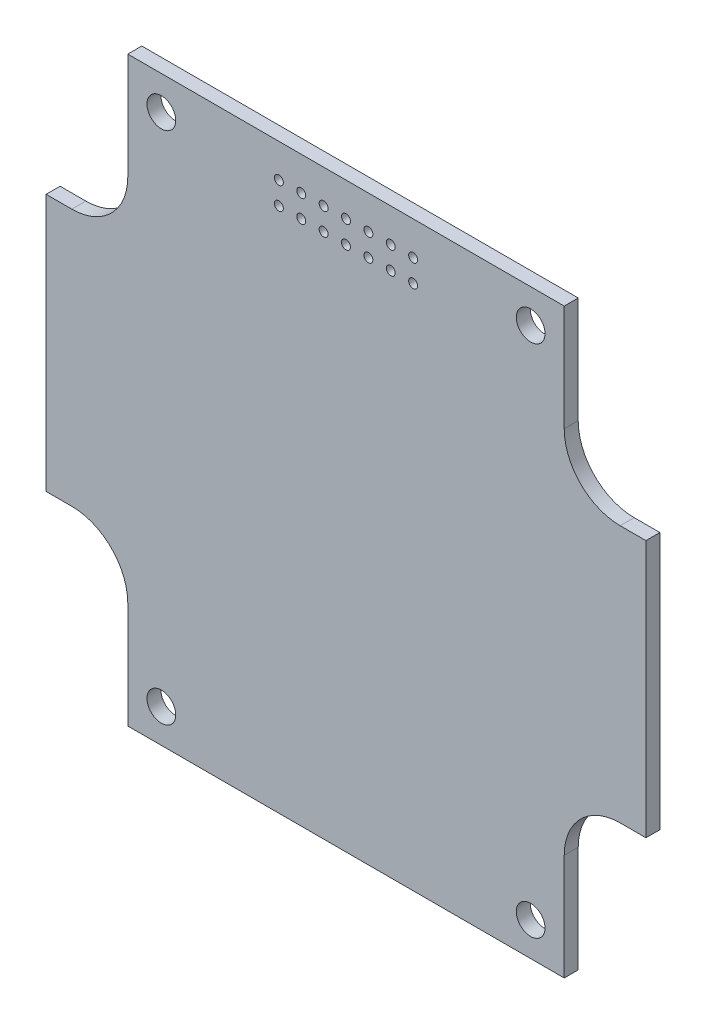
SolidWorks part; units mm, degrees
ref_plane "Front Plane" through (0, 0, 0) normal (0, 0, 1) x (1, 0, 0)
ref_plane "Top Plane" through (0, 0, 0) normal (0, 1, 0) x (1, 0, 0)
ref_plane "Right Plane" through (0, 0, 0) normal (1, 0, 0) x (0, 0, -1)
sketch "Sketch1" plane through (0, 0, 0) normal (0, 0, 1) x (1, 0, 0)
  line L0 (0, 47.625) -> (0, 18.415)
  line L1 (0, 18.415) -> (2.921, 18.415)
  line L2 (9.271, 12.065) -> (9.271, 0)
  line L3 (9.271, 0) -> (58.801, 0)
  line L4 (0, 33.02) -> (34.036, 33.02) construction
  line L5 (34.036, 33.02) -> (34.036, 0) construction
  line L6 (58.801, 12.065) -> (58.801, 0)
  line L7 (68.072, 18.415) -> (65.151, 18.415)
  line L8 (68.072, 47.625) -> (68.072, 18.415)
  line L9 (9.271, 53.975) -> (9.271, 66.04)
  line L10 (0, 47.625) -> (2.921, 47.625)
  line L11 (9.271, 66.04) -> (58.801, 66.04)
  line L12 (68.072, 47.625) -> (65.151, 47.625)
  line L13 (58.801, 53.975) -> (58.801, 66.04)
  arc A0 (2.921, 18.415) -> (9.271, 12.065) centre (2.921, 12.065) cw
  arc A1 (65.151, 18.415) -> (58.801, 12.065) centre (65.151, 12.065) ccw
  arc A2 (58.801, 53.975) -> (65.151, 47.625) centre (65.151, 53.975) ccw
  arc A3 (9.271, 53.975) -> (2.921, 47.625) centre (2.921, 53.975) cw
  point P21 (68.072, 33.02)
  point P23 (58.801, 47.625)
  dimension "D5" = 6.35
  dimension "D1" = 24.765
  dimension "D2" = 34.036
  dimension "D3" = 33.02
  dimension "D4" = 14.605
extrude "Boss-Extrude1" add sketch "Sketch1" along normal blind 1.5875
sketch "Sketch3" plane through (0, 0, 1.5875) normal (0, 0, 1) x (1, 0, 0)
  line L113 (0, 33.02) -> (68.072, 33.02) construction
  line L114 (68.072, 33.02) -> (34.036, 33.02) construction
  line L115 (34.036, 33.02) -> (34.036, 66.04) construction
  line L125 (65.151, 18.415) -> (68.072, 18.415)
  line L126 (58.801, 0) -> (58.801, 12.065)
  line L127 (9.271, 0) -> (58.801, 0)
  line L128 (9.271, 12.065) -> (9.271, 0)
  line L129 (0, 18.415) -> (2.921, 18.415)
  line L130 (0, 47.625) -> (0, 18.415)
  line L131 (2.921, 47.625) -> (0, 47.625)
  line L132 (9.271, 66.04) -> (9.271, 53.975)
  line L133 (58.801, 66.04) -> (9.271, 66.04)
  line L134 (68.072, 47.625) -> (65.151, 47.625)
  line L135 (58.801, 53.975) -> (58.801, 66.04)
  line L136 (68.072, 18.415) -> (68.072, 47.625)
  line L137 (65.151, 18.415) -> (68.072, 18.415)
  line L138 (58.801, 0) -> (58.801, 12.065)
  line L139 (9.271, 0) -> (58.801, 0)
  line L140 (9.271, 12.065) -> (9.271, 0)
  line L141 (0, 18.415) -> (2.921, 18.415)
  line L142 (0, 47.625) -> (0, 18.415)
  line L143 (2.921, 47.625) -> (0, 47.625)
  line L144 (9.271, 66.04) -> (9.271, 53.975)
  line L145 (58.801, 66.04) -> (9.271, 66.04)
  line L146 (68.072, 47.625) -> (65.151, 47.625)
  line L147 (58.801, 53.975) -> (58.801, 66.04)
  line L148 (68.072, 18.415) -> (68.072, 47.625)
  circle A36 centre (13.081, 62.23) radius 1.6319
  circle A37 centre (54.991, 62.23) radius 1.632
  circle A38 centre (54.991, 3.81) radius 1.632
  circle A39 centre (13.081, 3.81) radius 1.6319
  arc A40 (65.151, 18.415) -> (58.801, 12.065) centre (65.151, 12.065) ccw
  arc A41 (9.271, 12.065) -> (2.921, 18.415) centre (2.921, 12.065) ccw
  arc A42 (2.921, 47.625) -> (9.271, 53.975) centre (2.921, 53.975) ccw
  arc A43 (58.801, 53.975) -> (65.151, 47.625) centre (65.151, 53.975) ccw
  arc A44 (65.151, 18.415) -> (58.801, 12.065) centre (65.151, 12.065) ccw
  arc A45 (9.271, 12.065) -> (2.921, 18.415) centre (2.921, 12.065) ccw
  arc A46 (2.921, 47.625) -> (9.271, 53.975) centre (2.921, 53.975) ccw
  arc A47 (58.801, 53.975) -> (65.151, 47.625) centre (65.151, 53.975) ccw
  dimension "D2" = 3.2639
  dimension "D3" = 3.81
  dimension "D4" = 3.81
  dimension "D1" = 0
extrude "Cut-Extrude1" cut sketch "Sketch3" against normal through all contours A37 | A38 | A39 | A36 region at (13.081, 62.23, 1.5875) region at (54.991, 62.23, 1.5875) region at (54.991, 3.81, 1.5875) region at (13.081, 3.81, 1.5875)
sketch "Sketch4" plane through (0, 0, 1.5875) normal (0, 0, 1) x (1, 0, 0)
  line L0 (32.004, 65.9195) -> (36.068, 65.9195) construction
  line L1 (36.068, 65.9195) -> (36.068, 56.0005) construction
  line L2 (36.068, 56.0005) -> (32.004, 56.0005) construction
  line L3 (32.004, 56.0005) -> (32.004, 65.9195) construction
  line L4 (34.036, 65.9195) -> (34.036, 56.0005) construction
  line L5 (34.036, 56.0005) -> (32.004, 56.0005) construction
  line L6 (32.004, 56.0005) -> (32.004, 60.96) construction
  line L7 (32.004, 60.96) -> (36.068, 60.96) construction
  line L8 (0, 33.02) -> (68.072, 33.02) construction
  line L9 (0, 47.625) -> (0, 18.415) construction
  line L10 (68.072, 18.415) -> (68.072, 47.625) construction
  line L11 (34.036, 66.04) -> (34.036, 33.02) construction
  line L12 (58.801, 66.04) -> (9.271, 66.04) construction
  circle A0 centre (34.036, 62.23) radius 0.508
  circle A1 centre (36.576, 62.23) radius 0.508
  circle A2 centre (39.116, 62.23) radius 0.508
  circle A3 centre (41.656, 62.23) radius 0.508
  circle A4 centre (36.576, 59.69) radius 0.508
  circle A5 centre (39.116, 59.69) radius 0.508
  circle A6 centre (41.656, 59.69) radius 0.508
  circle A7 centre (34.036, 59.69) radius 0.508
  circle A8 centre (31.496, 62.23) radius 0.508
  circle A9 centre (28.956, 62.23) radius 0.508
  circle A10 centre (26.416, 62.23) radius 0.508
  circle A11 centre (31.496, 59.69) radius 0.508
  circle A12 centre (28.956, 59.69) radius 0.508
  circle A13 centre (26.416, 59.69) radius 0.508
  circle A14 centre (34.036, 59.69) radius 0.508
  dimension "D1" = 1.016
  dimension "D4" = 4
  dimension "D2" = 0
  dimension "D3" = 1.27
  dimension "D8" = 0
  dimension "D9" = 27.94
  dimension "D5" = 2
  dimension "D6" = 4
  dimension "D7" = 2
extrude "Cut-Extrude2" cut sketch "Sketch4" against normal through all contours A0 | A7 | A10 | A13 | A9 | A12 | A11 | A4 | A5 | A6 | A3 | A2 | A1 | A8 region at (34.036, 62.23, 1.5875) region at (36.576, 62.23, 1.5875) region at (39.116, 62.23, 1.5875) region at (41.656, 62.23, 1.5875) region at (36.576, 59.69, 1.5875) region at (39.116, 59.69, 1.5875) region at (41.656, 59.69, 1.5875) region at (34.036, 59.69, 1.5875) region at (31.496, 62.23, 1.5875) region at (28.956, 62.23, 1.5875) region at (26.416, 62.23, 1.5875) region at (31.496, 59.69, 1.5875) region at (28.956, 59.69, 1.5875) region at (26.416, 59.69, 1.5875)
